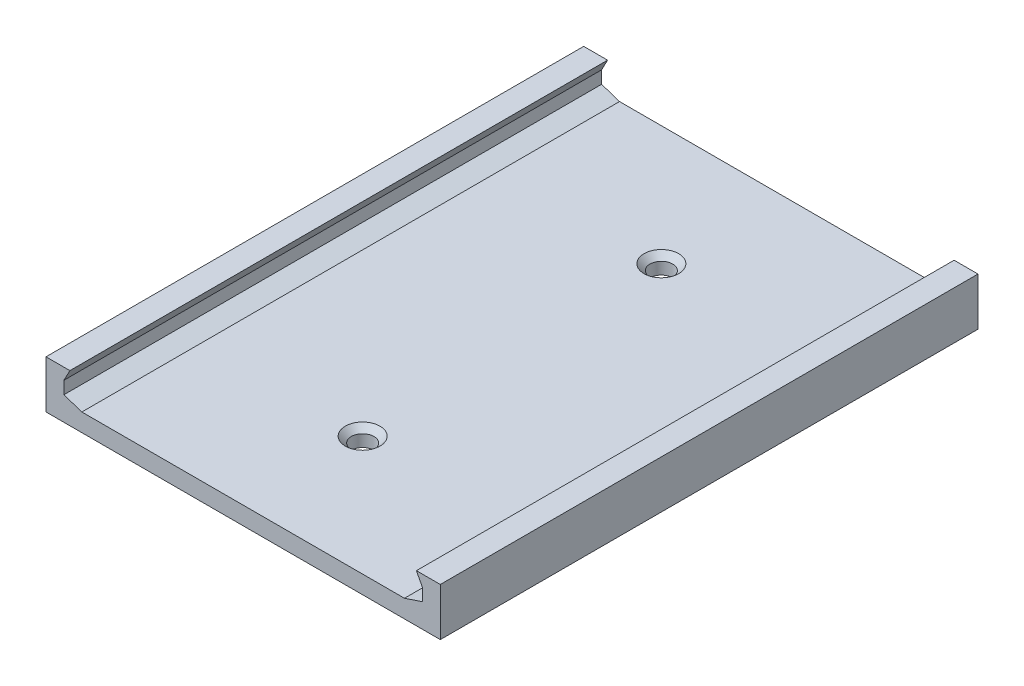
SolidWorks part; units mm, degrees
ref_plane "Спереди" through (0, 0, 0) normal (0, 0, 1) x (1, 0, 0)
ref_plane "Сверху" through (0, 0, 0) normal (0, 1, 0) x (1, 0, 0)
ref_plane "Справа" through (0, 0, 0) normal (1, 0, 0) x (0, 0, -1)
sketch "Эскиз1" plane through (0, 0, 0) normal (0, 0, 1) x (1, 0, 0)
  line L1 (0, 0) -> (66, 0)
  line L2 (0, 0) -> (0, 3)
  line L3 (0, 3) -> (66, 3)
  line L4 (66, 0) -> (66, 3)
  dimension "D1" = 66
  dimension "D2" = 3
extrude "base" add sketch "Эскиз1" along normal blind 90
sketch "Эскиз2" plane through (0, 0, 0) normal (0, 0, 1) x (1, 0, 0)
  line L0 (66, 3) -> (0, 3) construction
  line L1 (0, 3) -> (6, 3)
  line L2 (0, 3) -> (0, 8)
  line L3 (0, 8) -> (4, 8)
  line L4 (6, 3) -> (3, 4)
  line L5 (3, 4) -> (3, 6.1)
  line L6 (3, 6.1) -> (4, 8)
  line L7 (33, 3) -> (33, 0) construction
  line L8 (0, 0) -> (66, 0) construction
  line L9 (63, 6.1) -> (62, 8)
  line L10 (63, 4) -> (63, 6.1)
  line L11 (60, 3) -> (63, 4)
  line L12 (66, 8) -> (62, 8)
  line L13 (66, 3) -> (66, 8)
  line L14 (66, 3) -> (60, 3)
  dimension "D1" = 4
  dimension "D2" = 5
  dimension "D3" = 2.1
  dimension "D4" = 6
  dimension "D5" = 3
  dimension "D6" = 1
extrude "rails" add sketch "Эскиз2" along normal blind 90
sketch "Эскиз3" plane through (0, 3, 0) normal (0, 1, 0) x (1, 0, 0)
  line L0 (33, 0) -> (33, -90) construction
  line L1 (60, 0) -> (6, 0) construction
  line L2 (60, -90) -> (6, -90) construction
  circle A0 centre (33, -20) radius 1.9
  circle A1 centre (33, -70) radius 1.9
  dimension "D3" = 3.8
  dimension "D1" = 20
  dimension "D2" = 20
extrude "holes" cut sketch "Эскиз3" against normal through all
chamfer "Фаска1" distance 1 distance2 1 2 edges at (33, 3, 21.9) (33, 3, 71.9)
